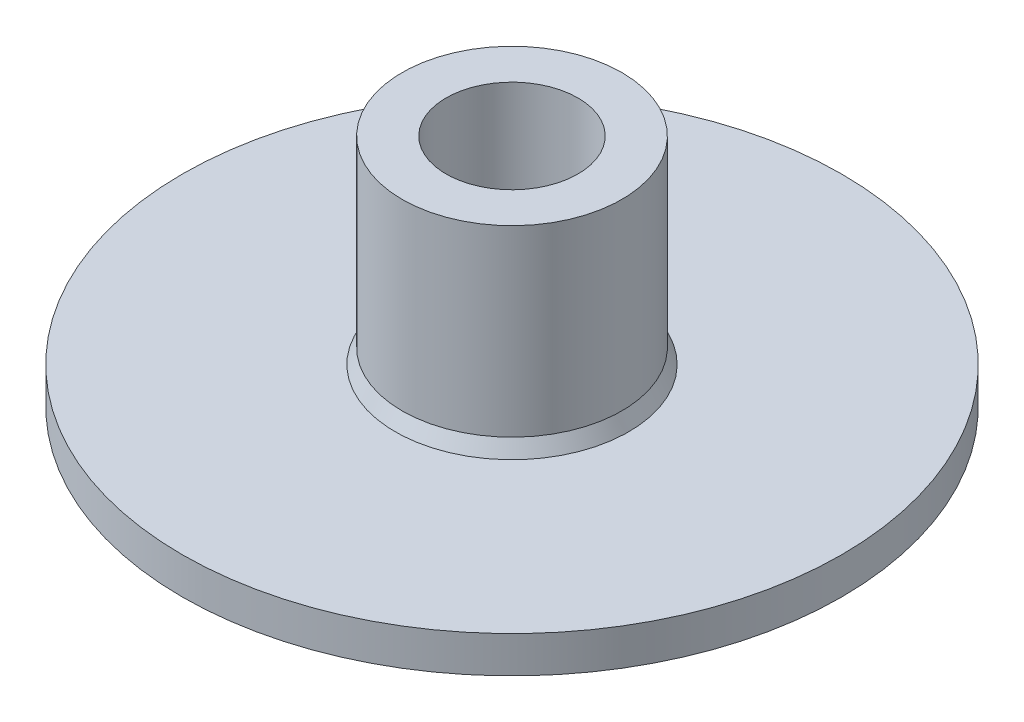
SolidWorks part; units mm, degrees
material "6061-T6 (SS)"
ref_plane "Piano frontale" through (0, 0, 0) normal (0, 0, 1) x (1, 0, 0)
ref_plane "Piano superiore" through (0, 0, 0) normal (0, 1, 0) x (1, 0, 0)
ref_plane "Piano destro" through (0, 0, 0) normal (1, 0, 0) x (0, 0, -1)
sketch "Schizzo1" plane through (0, 0, 0) normal (0, 0, 1) x (1, 0, 0)
  line L0 (0, 0) -> (0, 31.7802) construction
  line L2 (-68, 0) -> (-68, 5)
  line L3 (-68, 5) -> (-15.9412, 5)
  line L4 (-15.9412, 5) -> (-15, 7)
  line L5 (-15, 7) -> (-15, 32)
  line L6 (-15, 32) -> (-9, 32)
  line L7 (-9, 32) -> (-9, 8.5)
  line L8 (-9, 8.5) -> (-13, 0)
  line L9 (-13, 0) -> (-24, 0)
  line L11 (-24, 0) -> (-68, 0)
  line L12 (-18.4, 0) -> (-18.4, 1.3)
  line L13 (-18.4, 1.3) -> (-16, 1.3)
  line L14 (-16, 1.3) -> (-16, 0)
  line L15 (-34.4, 0) -> (-34.4, 1.3)
  line L16 (-34.4, 1.3) -> (-32, 1.3)
  line L17 (-32, 1.3) -> (-32, 0)
  line L18 (-68, 0) -> (-68, 26) construction
  line L21 (-29.5, 0) -> (-29.5, 1.3)
  line L23 (-29.5, 1.3) -> (-27.1, 1.3)
  line L24 (-27.1, 1.3) -> (-27.1, 0)
  line L25 (-45, 0) -> (-45, 5)
  point P3 (-9, 20.25)
  dimension "D2" = 26
  dimension "D3" = 18
  dimension "D5" = 5
  dimension "D7" = 30
  dimension "D8" = 25
  dimension "D9" = 27
  dimension "D10" = 8.5
  dimension "D11" = 2.4
  dimension "D12" = 1.3
  dimension "D13" = 32
  dimension "D14" = 64
  dimension "D15" = 2.5
  dimension "D16" = 90
revolve "Rivoluzione1" add sketch "Schizzo1" angle 360 about L0 region at (-44.5183, 2.5, 0)
fillet "Raccordo2" radius 0.2 6 edges at (0, 1.3, -18.4) (0, 1.3, -16) (0, 1.3, -29.5) (0, 1.3, -27.1) (0, 1.3, -34.4) (0, 1.3, -32)
